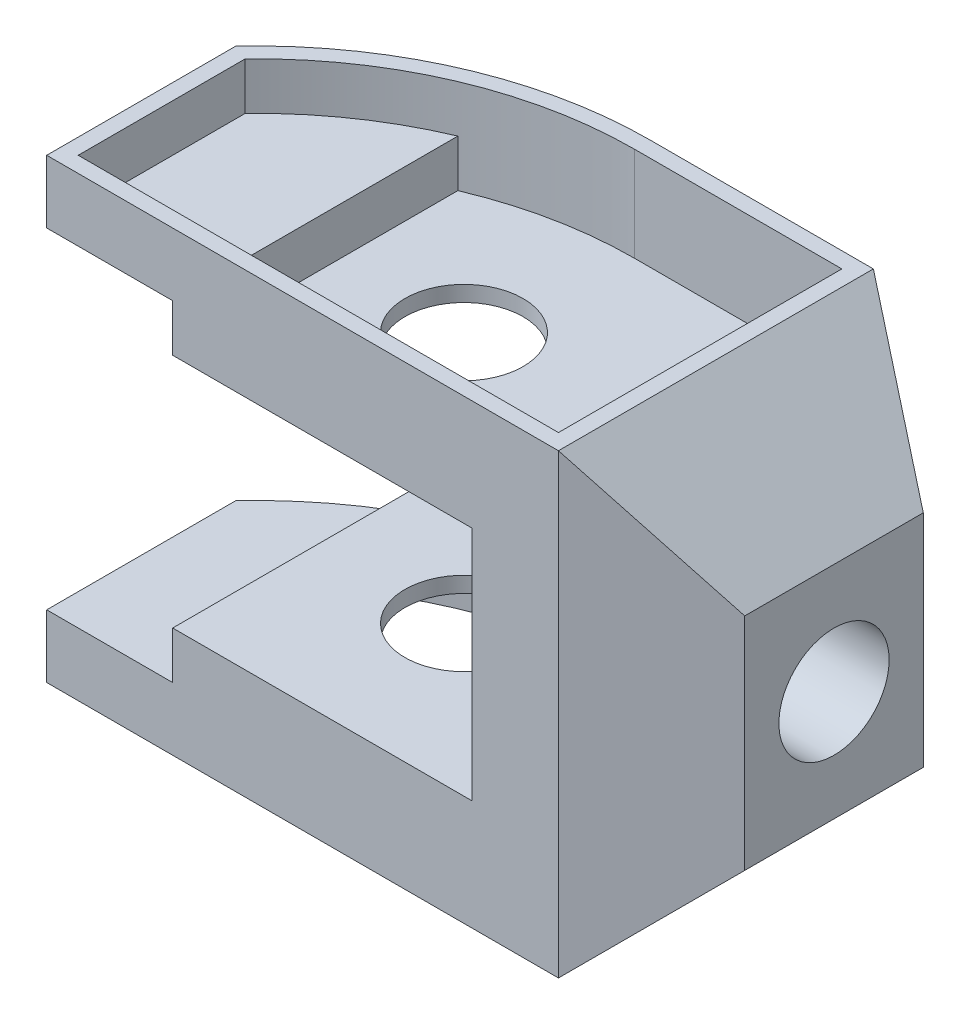
SolidWorks part; units mm, degrees
material "1060 Alloy"
ref_plane "Front Plane" through (0, 0, 0) normal (0, 0, 1) x (1, 0, 0)
ref_plane "Top Plane" through (0, 0, 0) normal (0, 1, 0) x (1, 0, 0)
ref_plane "Right Plane" through (0, 0, 0) normal (1, 0, 0) x (0, 0, -1)
sketch "Sketch1" plane through (0, 0, 0) normal (0, 1, 0) x (1, 0, 0)
  line L0 (0, 0) -> (65, 0)
  line L1 (65, 0) -> (80, 8.6603)
  line L2 (80, 8.6603) -> (80, 31.3397)
  line L3 (80, 31.3397) -> (65, 40)
  line L4 (65, 40) -> (36.6606, 40)
  line L5 (0, 0) -> (0, 24)
  arc A0 (36.6606, 40) -> (0, 24) centre (36.6606, -10) ccw
  circle A1 centre (34, 19) radius 7.5
  point P11 (0, 0)
  point P12 (0, 0)
  dimension "D6" = 50
  dimension "D7" = 15
  dimension "D1" = 65
  dimension "D2" = 30
  dimension "D3" = 24
  dimension "D4" = 30
  dimension "D5" = 40
  dimension "D8" = 19
  dimension "D9" = 15
  dimension "D10" = 15
  dimension "D11" = 31
extrude "Boss-Extrude1" add sketch "Sketch1" along normal blind 58
sketch "Sketch4" plane through (0, 0, -40) normal (0, 0, -1) x (-1, 0, 0)
  line L0 (0, 58) -> (0, 0) construction
  line L1 (-16, 44) -> (-54, 44)
  line L2 (0, 44) -> (0, 14)
  line L3 (-16, 14) -> (-54, 14)
  line L4 (-54, 44) -> (-54, 14)
  line L5 (0, 58) -> (-36.6606, 58) construction
  line L6 (0, 50) -> (-16, 50)
  line L7 (0, 50) -> (0, 8)
  line L8 (0, 8) -> (-16, 8)
  line L9 (-16, 50) -> (-16, 44)
  line L10 (-36.6606, 0) -> (0, 0) construction
  line L11 (-65, 58) -> (-65, 0) construction
  line L12 (-16, 14) -> (-16, 8)
  line M7 (-36.6606, 0) -> (-36.6606, 58)
  dimension "D1" = 8
  dimension "D2" = 8
  dimension "D3" = 11
  dimension "D4" = 6
  dimension "D5" = 6
  dimension "D6" = 16
extrude "Cut-Extrude1" cut sketch "Sketch4" against normal through all contours L1 L4 L3 M7 | L3 L12 L8 L7 L2 L6 L9 L1 M7 region at (16.7949, 29, -40) region at (45.3303, 29, -40)
sketch "Sketch5" plane through (80, 0, 0) normal (1, 0, 0) x (0, 0, -1)
  line L0 (8.6603, 58) -> (31.3397, 58) construction
  line L1 (0, 58) -> (0, 0) construction
  circle A0 centre (20, 29) radius 7
  point P4 (0, 0)
  point P6 (18.665, 28.1755)
  dimension "D1" = 14
  dimension "D2" = 29
  dimension "D3" = 20
extrude "Cut-Extrude2" cut sketch "Sketch5" against normal through all
sketch "Sketch7" plane through (0, 0, -40) normal (0, 0, -1) x (-1, 0, 0)
  line L0 (-80, 58) -> (-80, 43)
  line L1 (-80, 58) -> (-80, 0) construction
  line L2 (-80, 43) -> (-65, 58)
  line L3 (-65, 58) -> (-80, 58)
  line L4 (-80, 0) -> (-80, 15)
  line L5 (-80, 15) -> (-65, 0)
  line L6 (-65, 0) -> (-80, 0)
  dimension "D1" = 45
  dimension "D2" = 45
extrude "Cut-Extrude3" cut sketch "Sketch7" against normal through all
sketch "Sketch8" plane through (0, 58, 0) normal (0, 1, 0) x (1, 0, 0)
  line L8 (63, 2) -> (63, 38)
  line L9 (63, 38) -> (36.6606, 38)
  line L10 (2, 23.2061) -> (2, 2)
  line L11 (2, 2) -> (63, 2)
  line L12 (63, 2) -> (63, 38)
  line L13 (63, 38) -> (36.6606, 38)
  line L14 (2, 23.2061) -> (2, 2)
  line L15 (2, 2) -> (63, 2)
  arc A2 (36.6606, 38) -> (2, 23.2061) centre (36.6606, -10) ccw
  arc A3 (36.6606, 38) -> (2, 23.2061) centre (36.6606, -10) ccw
  dimension "D1" = 2
extrude "Cut-Extrude4" cut sketch "Sketch8" against normal blind 6
sketch "Sketch9" plane through (0, 52, 0) normal (0, 1, 0) x (1, 0, 0)
  line L0 (18, 2) -> (18, 34.2242)
  line L1 (2, 2) -> (63, 2) construction
  line L2 (0, 24) -> (0, 0) construction
  line L19 (63, 2) -> (63, 38)
  line L20 (63, 38) -> (36.6606, 38)
  line L21 (2, 23.2061) -> (2, 2)
  line L22 (2, 2) -> (63, 2)
  line L23 (63, 2) -> (63, 38)
  line L24 (63, 38) -> (36.6606, 38)
  line L26 (18, 2) -> (63, 2)
  arc A0 (36.6606, 38) -> (2, 23.2061) centre (36.6606, -10) ccw construction
  arc A5 (36.6606, 38) -> (2, 23.2061) centre (36.6606, -10) ccw
  arc A6 (36.6606, 38) -> (18, 34.2242) centre (36.6606, -10) ccw
  dimension "D1" = 18
  dimension "D2" = 2
extrude "Cut-Extrude6" cut sketch "Sketch9" against normal blind 6
sketch "Sketch10" plane through (0, 0, 0) normal (0, -1, 0) x (1, 0, 0)
  line L4 (18, -2) -> (18, -34.2242)
  line L8 (36.6606, -38) -> (63, -38)
  line L9 (63, -38) -> (63, -2)
  line L10 (63, -2) -> (2, -2)
  line L11 (2, -2) -> (2, -23.2061)
  line L12 (36.6606, -38) -> (63, -38)
  line L13 (63, -38) -> (63, -2)
  line L14 (63, -2) -> (2, -2)
  line L15 (2, -2) -> (2, -23.2061)
  arc A2 (2, -23.2061) -> (36.6606, -38) centre (36.6606, 10) ccw
  arc A3 (2, -23.2061) -> (36.6606, -38) centre (36.6606, 10) ccw
  circle M12 centre (34, -19) radius 7.5
  dimension "D2" = 16
  dimension "D1" = 2
extrude "Cut-Extrude8" cut sketch "Sketch10" against normal blind 6 contours L15 A3 L4 L14 region at (10.5272, 0, -15.9419)
extrude "Cut-Extrude9" cut sketch "Sketch10<4>" against normal blind 12 contours L4 A3 L12 L13 L14 M12 region at (41.5996, 0, -19.8499)
sketch "Sketch10<4>" plane through (0, 0, 0) normal (0, -1, 0) x (1, 0, 0) same geometry as "Sketch10"
equation "\"a\"= 58"
equation "\"b\"= 40"
equation "\"c\"= 65"
